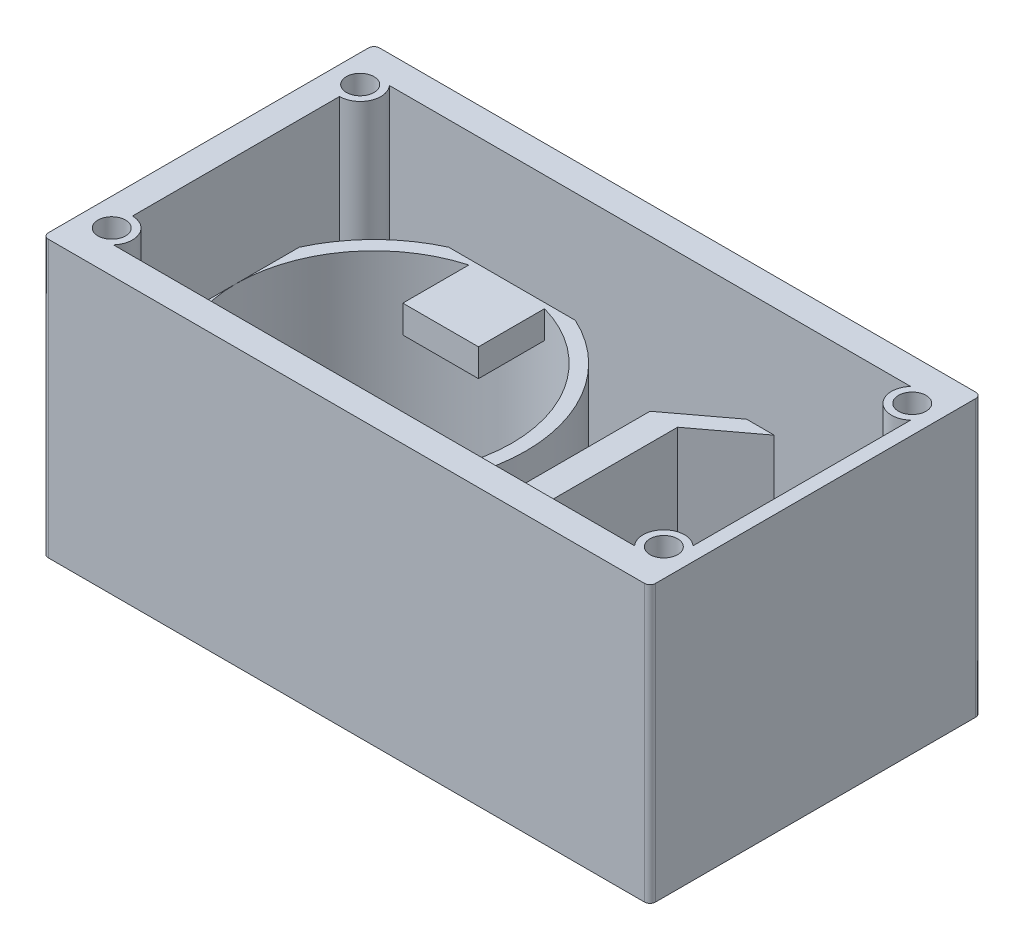
SolidWorks part; units mm, degrees
ref_plane "Front Plane" through (0, 0, 0) normal (0, 0, 1) x (1, 0, 0)
ref_plane "Top Plane" through (0, 0, 0) normal (0, 1, 0) x (1, 0, 0)
ref_plane "Right Plane" through (0, 0, 0) normal (1, 0, 0) x (0, 0, -1)
sketch "Sketch1" plane through (0, 0, 0) normal (0, 1, 0) x (1, 0, 0)
  line L1 (-11, -6) -> (11, -6)
  line L2 (-11, -6) -> (-11, 6)
  line L3 (-11, 6) -> (11, 6)
  line L4 (11, -6) -> (11, 6)
  line L5 (-11, -6) -> (11, 6) construction
  line L6 (-11, 6) -> (11, -6) construction
  point P0 (0, 0)
  dimension "D1" = 12
  dimension "D2" = 22
extrude "Boss-Extrude1" add sketch "Sketch1" along normal blind 10
sketch "Sketch2" plane through (0, 10, 0) normal (0, 1, 0) x (1, 0, 0)
  line L0 (11, 6) -> (-11, 6) construction
  line L1 (10.5, -5) -> (-10, -5)
  line L2 (10.5, -5) -> (10.5, 5)
  line L3 (10.5, 5) -> (-10, 5)
  line L4 (-10, -5) -> (-10, 5)
  line L5 (10.5, -5) -> (-10, 5) construction
  line L6 (10.5, 5) -> (-10, -5) construction
  line L7 (11, -6) -> (11, 6) construction
  point P0 (0.25, 0)
  dimension "D1" = 20.5
  dimension "D2" = 10
  dimension "D3" = 1
  dimension "D4" = 0.5
extrude "Cut-Extrude1" cut sketch "Sketch2" against normal blind 9 contours L4 L3 L2 L1
fillet "Fillet1" radius 0.2 4 edges at (-11, 5, -6) (11, 5, -6) (11, 5, 6) (-11, 5, 6)
sketch "Sketch3" plane through (0, 0, 0) normal (0, -1, 0) x (-1, 0, 0)
  circle A0 centre (5, 0) radius 5
extrude "Cut-Extrude2" cut sketch "Sketch3" against normal through all
sketch "Sketch4" plane through (0, 0, 0) normal (0, -1, 0) x (-1, 0, 0)
  circle A0 centre (-1, 0) radius 0.5
extrude "Cut-Extrude3" cut sketch "Sketch4" against normal through all
sketch "Sketch5" plane through (0, 0, 0) normal (0, -1, 0) x (-1, 0, 0)
  line L0 (-10.5, -5) -> (-10.5, 5) construction
  circle A0 centre (-6.5, 0) radius 2
  dimension "D1" = 4
extrude "Cut-Extrude4" cut sketch "Sketch5" against normal through all
sketch "Sketch6" plane through (0, 1, 0) normal (0, 1, 0) x (1, 0, 0)
  line L0 (2.5, 9.9437) -> (2.5, -10.995) construction
  line L1 (10.5, -5) -> (10.5, 5) construction
  line L2 (-14.9978, 3.5) -> (28.4787, 3.5) construction
  line L3 (20.7123, -3.5) -> (-19.3378, -3.5) construction
  line L4 (0, 0) -> (34.8745, 0) construction
  line L5 (1.5, 9.9437) -> (1.5, -10.995) construction
  line L6 (4.5, 12.7723) -> (4.5, -14.9146) construction
  line L7 (3.5, 10.9096) -> (3.5, -15.2533) construction
  line L8 (2.5, -3.5) -> (2.5, 3.5)
  line L9 (2.5, 3.5) -> (4.5, 5)
  line L10 (10.5, 5) -> (-5, 5) construction
  line L11 (4.5, 5) -> (3.5, 5)
  line L12 (3.5, 5) -> (1.5, 3.5)
  line L13 (1.5, 3.5) -> (1.5, -3.5)
  line L14 (1.5, -3.5) -> (3.5, -5)
  line L15 (10.5, -5) -> (-5, -5) construction
  line L16 (3.5, -5) -> (4.5, -5)
  line L17 (4.5, -5) -> (2.5, -3.5)
  dimension "D1" = 8
  dimension "D2" = 3.5
  dimension "D3" = 3.5
  dimension "D4" = 1
  dimension "D5" = 2
  dimension "D6" = 1
extrude "Boss-Extrude2" add sketch "Sketch6" along normal blind 5
sketch "Sketch9" plane through (0, 1, 0) normal (0, 1, 0) x (1, 0, 0)
  circle A0 centre (-5, 0) radius 5.5
  circle A1 centre (-5, 0) radius 5
extrude "Boss-Extrude3" add sketch "Sketch9" along normal blind 5
sketch "Sketch10" plane through (0, 1, 0) normal (0, 1, 0) x (1, 0, 0)
  circle A0 centre (1, 0) radius 1
  circle A1 centre (1, 0) radius 0.5
extrude "Boss-Extrude4" add sketch "Sketch10" along normal blind 2
sketch "Sketch12" plane through (0, 3, 0) normal (0, 1, 0) x (1, 0, 0)
  circle A0 centre (1, 0) radius 0.5
extrude "Boss-Extrude6" add sketch "Sketch12" against normal blind 1
sketch "Sketch13" plane through (0, 1, 0) normal (0, 1, 0) x (1, 0, 0)
  circle A0 centre (10, 4.5) radius 0.75
  circle A1 centre (10, 4.5) radius 0.5
extrude "Boss-Extrude7" add sketch "Sketch13" along normal blind 9
sketch "Sketch14" plane through (0, 0, 0) normal (0, -1, 0) x (-1, 0, 0)
  circle A0 centre (-10, 4.5) radius 0.5
extrude "Cut-Extrude5" cut sketch "Sketch14" against normal through all
mirror "Mirror1" about plane through (0, 0, 0) normal (1, 0, 0) of "Cut-Extrude5", "Boss-Extrude7"
mirror "Mirror2" about plane through (0, 0, 0) normal (0, 0, 1) of "Mirror1"
sketch "Sketch15" plane through (0, 6, 0) normal (0, 1, 0) x (1, 0, 0)
  line L0 (-6.3706, 2.4148) -> (-6.3706, 5.5363)
  line L1 (-6.3706, -5.5363) -> (-3.6294, -5.5363)
  line L2 (-6.3706, -5.5363) -> (-6.3706, -2.4148)
  line L3 (-6.3706, 5.5363) -> (-3.6294, 5.5363)
  line L4 (-3.6294, -5.5363) -> (-3.6294, -2.4148)
  line L7 (-6.3706, -2.4148) -> (-3.6294, -2.4148)
  line L9 (-6.3706, 2.4148) -> (-3.6294, 2.4148)
  line L15 (-3.6294, 2.4148) -> (-3.6294, 5.5363)
  point P0 (-5, 0)
  point P1 (-5, 0)
  point P9 (-5, 0)
extrude "Boss-Extrude8" add sketch "Sketch15" against normal blind 1
sketch "Sketch16" plane through (0, 0, 0) normal (0, -1, 0) x (1, 0, 0)
  circle A0 centre (1, 0) radius 0.5
